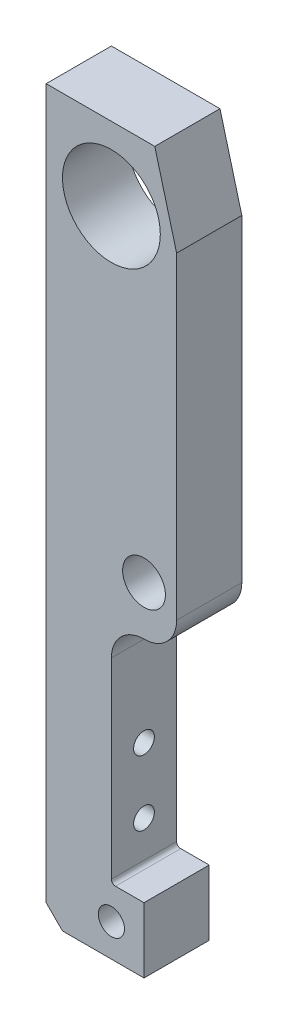
SolidWorks part; units mm, degrees
material "Alum 6061"
ref_plane "Front Plane" through (0, 0, 0) normal (0, 0, 1) x (1, 0, 0)
ref_plane "Top Plane" through (0, 0, 0) normal (0, 1, 0) x (1, 0, 0)
ref_plane "Right Plane" through (0, 0, 0) normal (1, 0, 0) x (0, 0, -1)
sketch "Sketch1" plane through (0, 0, 0) normal (0, 0, 1) x (1, 0, 0)
  line L1 (-12.7, 70.6438) -> (12.7, 70.6438)
  line L2 (-12.7, 70.6438) -> (-12.7, -70.6437)
  line L3 (-12.7, -70.6437) -> (12.7, -70.6437)
  line L4 (12.7, 70.6438) -> (12.7, -70.6437)
  line L5 (-12.7, 70.6438) -> (12.7, -70.6437) construction
  line L6 (-12.7, -70.6437) -> (12.7, 70.6438) construction
  point P0 (0, 0)
  dimension "Width" = 25.4
  dimension "Height" = 141.2875
extrude "Extrude1" add sketch "Sketch1" along normal mid plane 12.7
sketch "Sketch2" plane through (0, 0, 6.35) normal (0, 0, 1) x (1, 0, 0)
  line L0 (12.7, 70.6438) -> (-12.7, 70.6438) construction
  circle A0 centre (0, 56.3563) radius 9.525
  dimension "D1" = 14.2875
  dimension "D2" = 19.05
extrude "Cut-Extrude1" cut sketch "Sketch2" against normal up to next
sketch "Sketch3" plane through (0, 0, 6.35) normal (0, 0, 1) x (1, 0, 0)
  line L0 (12.7, -70.6437) -> (12.7, 70.6438) construction
  line L1 (6.35, -57.9437) -> (0.7938, -57.9437)
  line L2 (12.7, -70.6437) -> (12.7, -13.4937)
  line L3 (12.7, -13.4937) -> (6.35, -13.4937)
  line L4 (0, -57.15) -> (0, -19.8437)
  line L5 (-12.7, -70.6437) -> (12.7, -70.6437) construction
  line L6 (6.35, -57.9437) -> (6.35, -70.6437)
  line L7 (6.35, -70.6437) -> (12.7, -70.6437)
  arc A0 (6.35, -13.4937) -> (0, -19.8437) centre (6.35, -19.8437) ccw
  arc A1 (0, -57.15) -> (0.7938, -57.9437) centre (0.7938, -57.15) ccw
  point P7 (0, -13.4937)
  dimension "D3" = 6.35
  dimension "D5" = 6.35
  dimension "D6" = 0.7937
  dimension "D1" = 12.7
  dimension "D2" = 57.15
  dimension "D4" = 12.7
extrude "Cut-Extrude2" cut sketch "Sketch3" against normal up to next
chamfer "Chamfer1" distance 15.875 angle 15 1 edges at (12.7, 70.6438, 0) first distance on face at (12.7, 28.575, 0)
hole_wizard "21/64 (0.32813) Diameter Hole1" positions "Sketch6" profile "Sketch7" hole size "21/64" standard "ANSI Inch" end condition up to next
sketch "Sketch6" plane through (0, 0, 6.35) normal (0, 0, 1) x (1, 0, 0)
  circle A0 centre (0, 56.3563) radius 9.525 construction
  point P0 (6.35, -3.9687)
  dimension "D2" = 60.325
  dimension "D1" = 6.35
sketch "Sketch7" plane through (6.35, -3.9687, 6.35) normal (1, 0, 0) x (0, -1, 0)
  line L0 (0, 0) -> (0, 12.7)
  line L1 (0, 12.7) -> (4.1673, 12.7)
  line L2 (4.1673, 12.7) -> (4.1673, 0)
  line L5 (4.1673, 0) -> (0, 0)
  line L11 (0, -6.35) -> (0, 107.95) construction
  dimension "Thru Hole Dia." = 8.3345
  dimension "Thru Hole Depth" = 12.7
hole_wizard "1/4-20 Tapped Hole1" positions "Sketch8" profile "Sketch9" tap size "1/4-20" standard "ANSI Inch" end condition up to next
sketch "Sketch8" plane through (0, 0, 6.35) normal (0, 0, 1) x (1, 0, 0)
  line L0 (-12.7, -70.6437) -> (6.35, -70.6437) construction
  line L1 (6.35, -57.9437) -> (6.35, -70.6437) construction
  point P0 (0, -64.2937)
  dimension "D1" = 6.35
  dimension "D2" = 6.35
sketch "Sketch9" plane through (0, -64.2937, 6.35) normal (1, 0, 0) x (0, -1, 0)
  line L0 (0, 0) -> (0, 12.7)
  line L1 (0, 12.7) -> (2.5527, 12.7)
  line L2 (2.5527, 12.7) -> (2.5527, 0)
  line L5 (2.5527, 0) -> (0, 0)
  line L11 (0, -6.35) -> (0, 107.95) construction
  dimension "Thru Tap Drill Dia." = 5.1054
  dimension "Thru Tap Drill Depth" = 12.7
cosmetic thread "Hole Thread1" parameters "D2"=6.35
hole_wizard "#10-32 Tapped Hole1" positions "Sketch12" profile "Sketch13" tap size "#10-32" standard "ANSI Inch"
sketch "Sketch12" plane through (-12.7, 0, 0) normal (-1, 0, 0) x (0, 0, 1)
  line L0 (6.35, -70.6437) -> (-6.35, -70.6437) construction
  point P0 (0, -50.0062)
  point P2 (0, -37.3062)
  dimension "D1" = 20.6375
  dimension "D2" = 12.7
sketch "Sketch13" plane through (-12.7, -50.0062, 0) normal (0, 1, 0) x (0, 0, 1)
  line L0 (0, 0) -> (0, 14.9293)
  line L1 (0, 14.9293) -> (2.0193, 13.716)
  line L2 (2.0193, 13.716) -> (2.0193, 0)
  line L5 (2.0193, 0) -> (0, 0)
  line L10 (0, 14.9293) -> (-2.0193, 13.716) construction
  line L11 (0, -6.35) -> (0, 107.95) construction
  dimension "Tap Drill Dia." = 4.0386
  dimension "Tap Drill Depth" = 13.716
  dimension "Drill Angle" = 118
cosmetic thread "Hole Thread2" parameters "D1"=9.652, "D2"=4.826
cosmetic thread "Hole Thread3" parameters "D1"=9.652, "D2"=4.826
fillet "Fillet1" radius 6.35 1 edges at (12.7, -13.4937, 0)
chamfer "Chamfer2" distance 3.175 angle 45 1 edges at (-12.7, -70.6437, 0)
